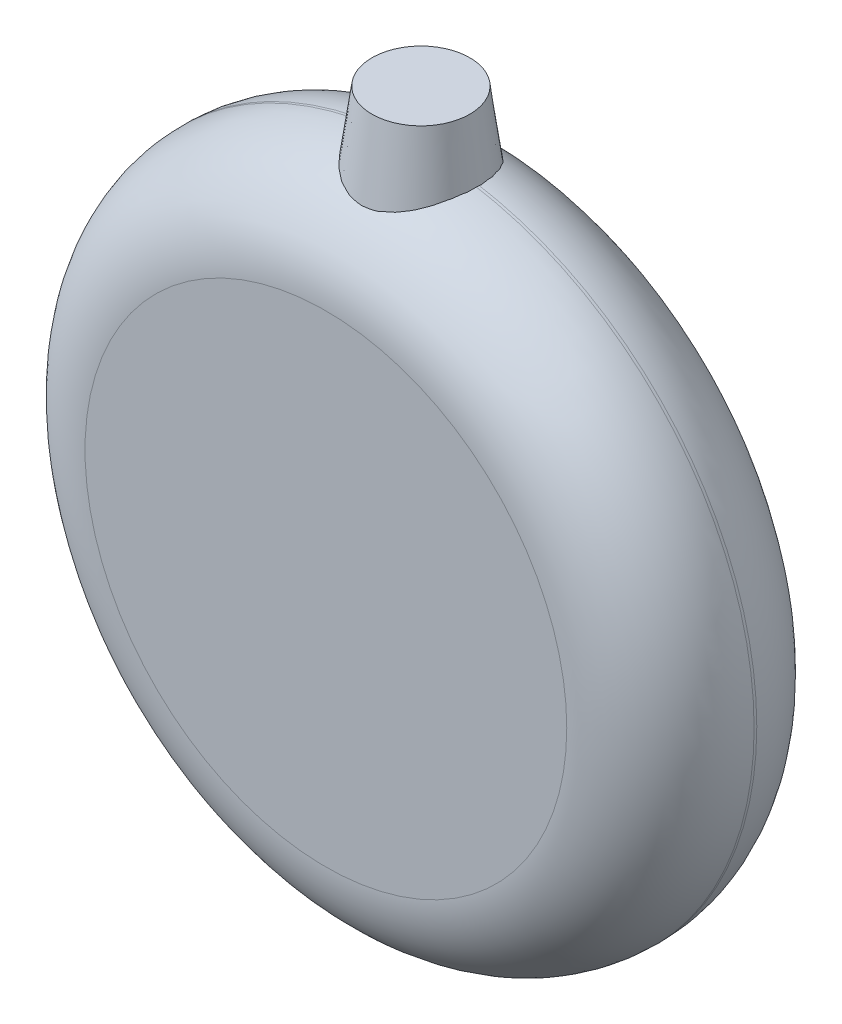
SolidWorks part; units mm, degrees
material "Polyester Resin"
ref_plane "Front Plane" through (0, 0, 0) normal (0, 0, 1) x (1, 0, 0)
ref_plane "Top Plane" through (0, 0, 0) normal (0, 1, 0) x (1, 0, 0)
ref_plane "Right Plane" through (0, 0, 0) normal (1, 0, 0) x (0, 0, -1)
sketch "Sketch1" plane through (0, 0, 0) normal (0, 0, 1) x (1, 0, 0)
  circle A0 centre (0, 0) radius 25
  dimension "D1" = 50
extrude "Boss-Extrude1" add sketch "Sketch1" along normal mid plane 14.2 contours A0 region at (0, 0, 0)
sketch "Sketch4" plane through (0, 0, 0) normal (0, 1, 0) x (1, 0, 0)
  circle A0 centre (0, 0) radius 4.5
  dimension "D1" = 9
extrude "Boss-Extrude2" add sketch "Sketch4" along normal blind 6 draft 8 from offset 23 separate body
fillet "Fillet2" radius 7 2 edges at (25, 0, 7.1) (25, 0, -7.1)
sketch "Sketch5" plane through (0, 0, -7.1) normal (0, 0, -1) x (-1, 0, 0)
  line L0 (18, 0) -> (-18, 0) construction
  line L1 (7.81, 0) -> (-7.81, 0) construction
  circle A0 centre (0, 0) radius 18 construction
  text T0 "M8N" font "Century Gothic" height 6.2
extrude "Boss-Extrude3" add sketch "Sketch5" along normal blind 0.1
